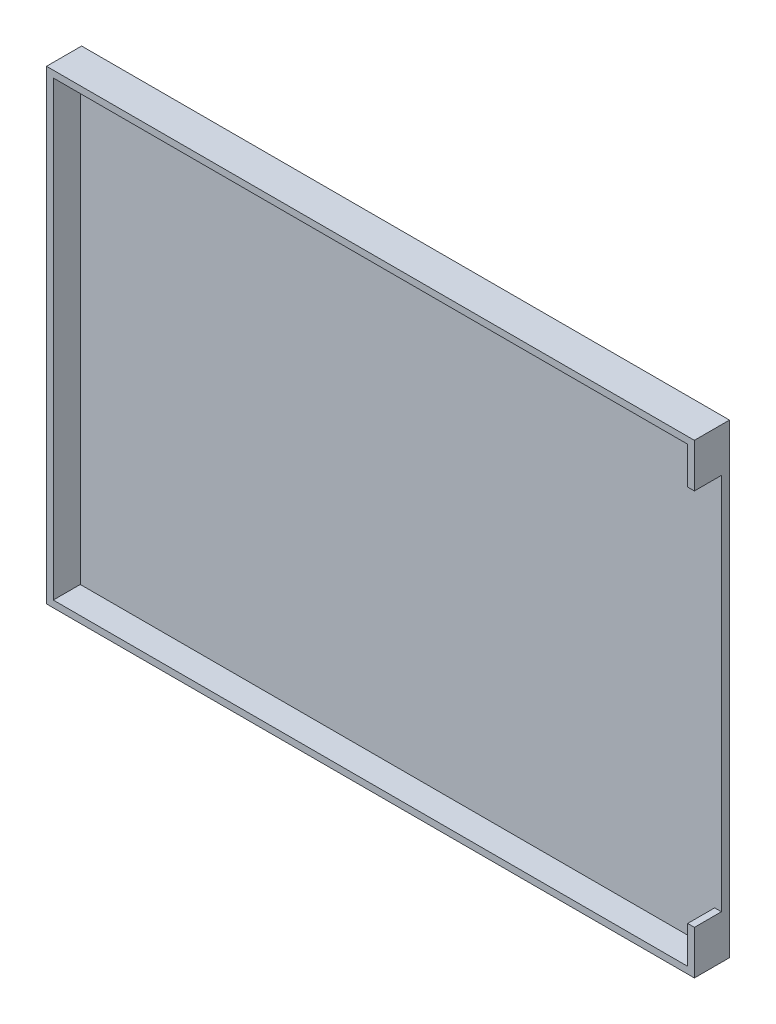
SolidWorks part; units mm, degrees
ref_plane "Спереди" through (0, 0, 0) normal (0, 0, 1) x (1, 0, 0)
ref_plane "Сверху" through (0, 0, 0) normal (0, 1, 0) x (1, 0, 0)
ref_plane "Справа" through (0, 0, 0) normal (1, 0, 0) x (0, 0, -1)
sketch "Эскиз1" plane through (0, 0, 0) normal (0, 0, 1) x (1, 0, 0)
  line L1 (-24, -17.25) -> (24, -17.25)
  line L2 (-24, -17.25) -> (-24, 17.25)
  line L3 (-24, 17.25) -> (24, 17.25)
  line L4 (24, -17.25) -> (24, 17.25)
  line L5 (-24, -17.25) -> (24, 17.25) construction
  line L6 (-24, 17.25) -> (24, -17.25) construction
  point P0 (0, 0)
  dimension "D1" = 34.5
  dimension "D2" = 48
extrude "Бобышка-Вытянуть1" add sketch "Эскиз1" along normal blind 0.6
sketch "Эскиз2" plane through (0, 0, 0.6) normal (0, 0, 1) x (1, 0, 0)
  line L4 (24, -17.25) -> (24, 17.25)
  line L5 (24, 17.25) -> (-24, 17.25)
  line L6 (-24, 17.25) -> (-24, -17.25)
  line L7 (-24, -17.25) -> (24, -17.25)
  line L9 (24, 17.25) -> (-24, 17.25)
  line L10 (-24, 17.25) -> (-24, -17.25)
  line L11 (-24, -17.25) -> (24, -17.25)
  line L12 (23.5, 16.75) -> (-23.5, 16.75)
  line L13 (-23.5, 16.75) -> (-23.5, -16.75)
  line L14 (-23.5, -16.75) -> (23.5, -16.75)
  line L15 (24, 16.75) -> (-23.5, 16.75) construction
  line L16 (-23.5, -16.75) -> (24, -16.75) construction
  line L17 (23.5, 16.75) -> (23.5, 14)
  line L18 (23.5, 14) -> (24, 14)
  line L19 (24, -17.25) -> (24, 17.25) construction
  line L20 (24, 14) -> (24, 17.25)
  line L21 (23.5, -16.75) -> (23.5, -14)
  line L22 (23.5, -14) -> (24, -14)
  line L23 (24, -14) -> (24, -17.25)
  dimension "D3" = 0.5
  dimension "D4" = 3.25
  dimension "D1" = 0
  dimension "D2" = 0.5
extrude "Бобышка-Вытянуть2" add sketch "Эскиз2" along normal blind 2
